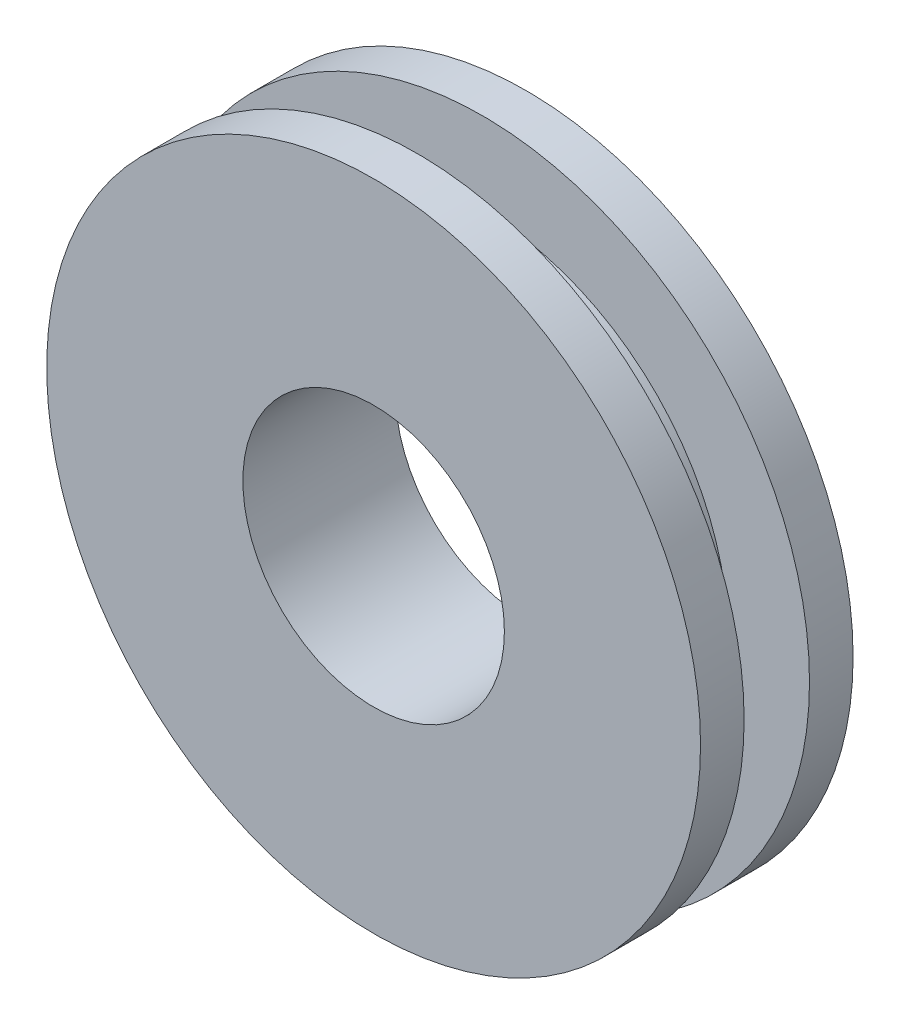
SolidWorks part; units mm, degrees
material "ABS"
ref_plane "Front Plane" through (0, 0, 0) normal (0, 0, 1) x (1, 0, 0)
ref_plane "Top Plane" through (0, 0, 0) normal (0, 1, 0) x (1, 0, 0)
ref_plane "Right Plane" through (0, 0, 0) normal (1, 0, 0) x (0, 0, -1)
sketch "Sketch1" plane through (0, 0, 0) normal (0, 0, 1) x (1, 0, 0)
  circle A0 centre (8.485, 8.485) radius 3
  circle A1 centre (8.485, 8.485) radius 2.25
  circle A2 centre (8.485, 8.485) radius 1.2
  dimension "D1" = 6
  dimension "D2" = 4.5
  dimension "D3" = 2.4
extrude "Boss-Extrude1" add sketch "Sketch1" along normal blind 0.4 contours A1 A2 | A0 A1 region at (5.5699, 8.485, 0) region at (6.2986, 8.485, 0)
extrude "Boss-Extrude4" add sketch "Sketch1<8>" along normal blind 0.6 from surface contours A1 A2 region at (6.2986, 8.485, 0) starting at face at (9.685, 8.485, 0.4)
sketch "Sketch1<8>" plane through (0, 0, 0) normal (0, 0, 1) x (1, 0, 0) same geometry as "Sketch1"
extrude "Boss-Extrude5" add sketch "Sketch1<9>" along normal blind 0.4 from surface contours A1 A2 | A0 A1 region at (5.5699, 8.485, 0) region at (6.2986, 8.485, 0) starting at face at (10.735, 8.485, 1)
sketch "Sketch1<9>" plane through (0, 0, 0) normal (0, 0, 1) x (1, 0, 0) same geometry as "Sketch1"
